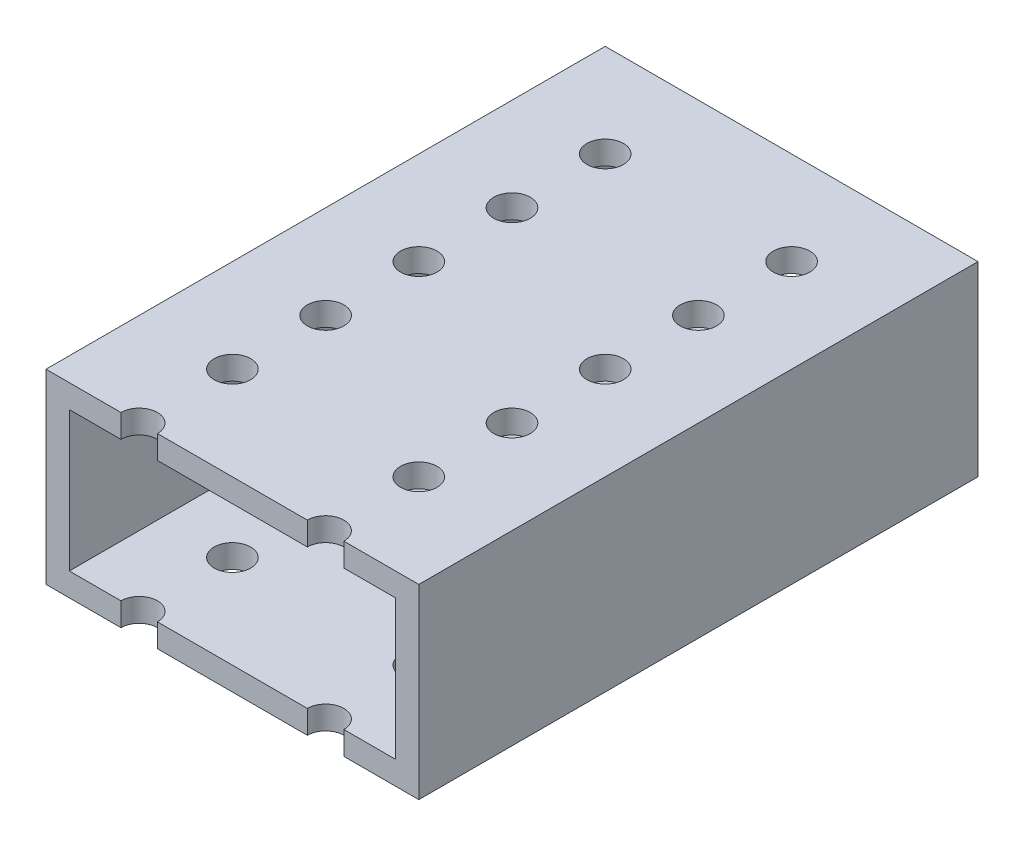
SolidWorks part; units mm, degrees
ref_plane "Front Plane" through (0, 0, 0) normal (0, 0, 1) x (1, 0, 0)
ref_plane "Top Plane" through (0, 0, 0) normal (0, 1, 0) x (1, 0, 0)
ref_plane "Right Plane" through (0, 0, 0) normal (1, 0, 0) x (0, 0, -1)
sketch "Sketch1" plane through (0, 0, 0) normal (0, 0, 1) x (1, 0, 0)
  line L1 (-25.4, -12.7) -> (25.4, -12.7)
  line L2 (-25.4, -12.7) -> (-25.4, 12.7)
  line L3 (-25.4, 12.7) -> (25.4, 12.7)
  line L4 (25.4, -12.7) -> (25.4, 12.7)
  line L5 (-25.4, -12.7) -> (25.4, 12.7) construction
  line L6 (-25.4, 12.7) -> (25.4, -12.7) construction
  point P0 (0, 0)
  dimension "D1" = 50.8
  dimension "D2" = 25.4
extrude "Boss-Extrude1" add sketch "Sketch1" along normal mid plane 76.2
shell "Shell1" thickness 3.175 removed face at (0, 0, -38.1) removed face at (0, 0, 38.1)
sketch "Sketch2" plane through (0, 0, 0) normal (0, 1, 0) x (1, 0, 0)
  line L0 (25.4, 38.1) -> (-25.4, 38.1) construction
  line L1 (-25.4, -38.1) -> (-25.4, 38.1) construction
  circle A0 centre (-12.7, 25.4) radius 2.4892
  circle A1 centre (12.7, 25.4) radius 2.4892
  circle A2 centre (12.7, 12.7) radius 2.4892
  circle A3 centre (12.7, 0) radius 2.4892
  circle A4 centre (12.7, -12.7) radius 2.4892
  circle A5 centre (12.7, -25.4) radius 2.4892
  circle A6 centre (12.7, -38.1) radius 2.4892
  circle A7 centre (-12.7, 12.7) radius 2.4892
  circle A8 centre (-12.7, 0) radius 2.4892
  circle A9 centre (-12.7, -12.7) radius 2.4892
  circle A10 centre (-12.7, -25.4) radius 2.4892
  circle A11 centre (-12.7, -38.1) radius 2.4892
  dimension "D1" = 4.9784
  dimension "D7" = 12.7
  dimension "D2" = 12.7
  dimension "D3" = 12.7
  dimension "D6" = 25.4
  dimension "D4" = 2
  dimension "D5" = 6
extrude "Cut-Extrude1" cut sketch "Sketch2" against normal mid plane 127
